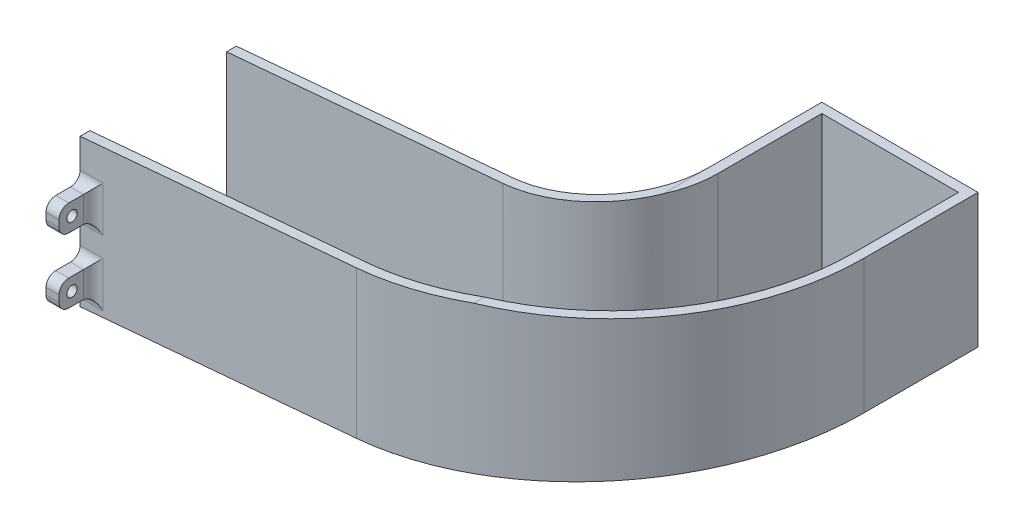
SolidWorks part; units mm, degrees
ref_plane "Front Plane" through (0, 0, 0) normal (0, 0, 1) x (1, 0, 0)
ref_plane "Top Plane" through (0, 0, 0) normal (0, 1, 0) x (1, 0, 0)
ref_plane "Right Plane" through (0, 0, 0) normal (1, 0, 0) x (0, 0, -1)
sketch "Sketch2" plane through (0, 0, 0) normal (0, 1, 0) x (1, 0, 0)
  line L1 (0, 0) -> (85, 0)
  line L2 (0, 0) -> (0, 48)
  line L3 (0, 48) -> (85, 48)
  line L8 (115, 78) -> (115, 113)
  line L9 (115, 113) -> (163, 113)
  line L10 (163, 78) -> (163, 113)
  arc A1 (85, 48) -> (115, 78) centre (85, 78) ccw
  arc A2 (85, 0) -> (163, 78) centre (85, 78) ccw
  point P9 (0, 0)
  point P11 (0, 0)
  dimension "D1" = 48
  dimension "D5" = 35
  dimension "D2" = 85
  dimension "D3" = 48
  dimension "D4" = 115
extrude "Boss-Extrude1" add sketch "Sketch2" along normal blind 60
sketch "Sketch3" plane through (0, 0, 0) normal (0, 0, 1) x (1, 0, 0)
  line L0 (0, 0) -> (200, 17.4977)
  line L2 (0, 60) -> (0, 0) construction
  line L3 (200, 0) -> (200, 17.4977)
  line L5 (0, 0) -> (200, 0)
  line L7 (0, 45.39) -> (0, 60)
  line L8 (0, 60) -> (200, 60)
  line L9 (0, 60) -> (85, 60) construction
  line L11 (163, 60) -> (85, 60) construction
  line L12 (0, 45.39) -> (115, 55.4512)
  line L13 (115, 55.4512) -> (200, 55.4512)
  line L14 (200, 55.4512) -> (200, 60)
  point P4 (140.9944, 57.1439)
  point P14 (154.6463, 60)
  point P17 (180.8999, 60)
  point P18 (132.5245, 57.8644)
  point P21 (113.8292, 56.2288)
  point P23 (0, 0)
  dimension "D1" = 45.39
  dimension "D2" = 200
  dimension "D3" = 5
extrude "Cut-Extrude1" cut sketch "Sketch3" against normal through all
shell "Shell4" thickness 3 removed face at (67.7517, 51.3175, -28.7169) removed face at (136.38, 55.4512, -76.1467)
sketch "Sketch15" plane through (3, 0, 0) normal (1, 0, 0) x (0, 0, -1)
  line L4 (45, 45.6525) -> (3, 45.6525)
  line L5 (45, 45.6525) -> (3, 45.6525)
  line L8 (3, 45.6525) -> (3, 3.2739)
  line L9 (3, 3.2739) -> (45, 3.2739)
  line L10 (45, 3.2739) -> (45, 45.6525)
  line L12 (3, 45.6525) -> (3, 3.2739)
  line L13 (3, 3.2739) -> (45, 3.2739)
  line L14 (45, 3.2739) -> (45, 45.6525)
  dimension "D1" = 0
extrude "Cut-Extrude8" cut sketch "Sketch15" against normal up to surface (3 mm away) up to face at (0, 22.695, -24)
sketch "Sketch16" plane through (0, 0, 0) normal (-1, 0, 0) x (0, 0, 1)
  line L1 (-1.5, 33.39) -> (10.5, 33.39)
  line L2 (-1.5, 33.39) -> (-1.5, 25.39)
  line L3 (-1.5, 25.39) -> (10.5, 25.39)
  line L4 (10.5, 33.39) -> (10.5, 25.39)
  line L5 (0, 45.39) -> (0, 0) construction
  line L7 (-3, 45.39) -> (0, 45.39) construction
  line L8 (-1.5, 13.39) -> (10.5, 13.39)
  line L13 (-1.5, 13.39) -> (-1.5, 5.39)
  line L14 (-1.5, 5.39) -> (10.5, 5.39)
  line L15 (10.5, 13.39) -> (10.5, 5.39)
  line L16 (-24, 0) -> (-24, 60) construction
  line L17 (-48, 0) -> (0, 0) construction
  line L18 (-58.5, 13.39) -> (-58.5, 5.39)
  line L19 (-46.5, 5.39) -> (-58.5, 5.39)
  line L20 (-46.5, 13.39) -> (-46.5, 5.39)
  line L21 (-46.5, 13.39) -> (-58.5, 13.39)
  line L22 (-58.5, 33.39) -> (-58.5, 25.39)
  line L23 (-46.5, 25.39) -> (-58.5, 25.39)
  line L24 (-46.5, 33.39) -> (-46.5, 25.39)
  line L25 (-46.5, 33.39) -> (-58.5, 33.39)
  circle A0 centre (6.5, 29.39) radius 1.6
  circle A2 centre (6.5, 9.39) radius 1.6
  circle A3 centre (-54.5, 9.39) radius 1.6
  circle A4 centre (-54.5, 29.39) radius 1.6
  point P10 (10.5, 29.39)
  dimension "D1" = 3.2
  dimension "D2" = 8
  dimension "D3" = 4
  dimension "D4" = 1.5
  dimension "D5" = 12
  dimension "D6" = 8
  dimension "D7" = 2
  dimension "D8" = 20
  dimension "D9" = 60
extrude "Boss-Extrude2" add sketch "Sketch16" against normal blind 4
fillet "Fillet1" radius 3 20 edges at (2, 5.39, 10.5) (2, 5.39, 0) (4, 9.39, 0) (2, 13.39, 10.5) (2, 13.39, 0) (2, 25.39, 10.5) (2, 25.39, 0) (4, 29.39, 0) (2, 33.39, 0) (2, 33.39, 10.5) (2, 13.39, -58.5) (2, 5.39, -58.5) (2, 5.39, -48) (4, 9.39, -48) (2, 13.39, -48) (4, 29.39, -48) (2, 25.39, -48) (2, 25.39, -58.5) (2, 33.39, -48) (2, 33.39, -58.5)
